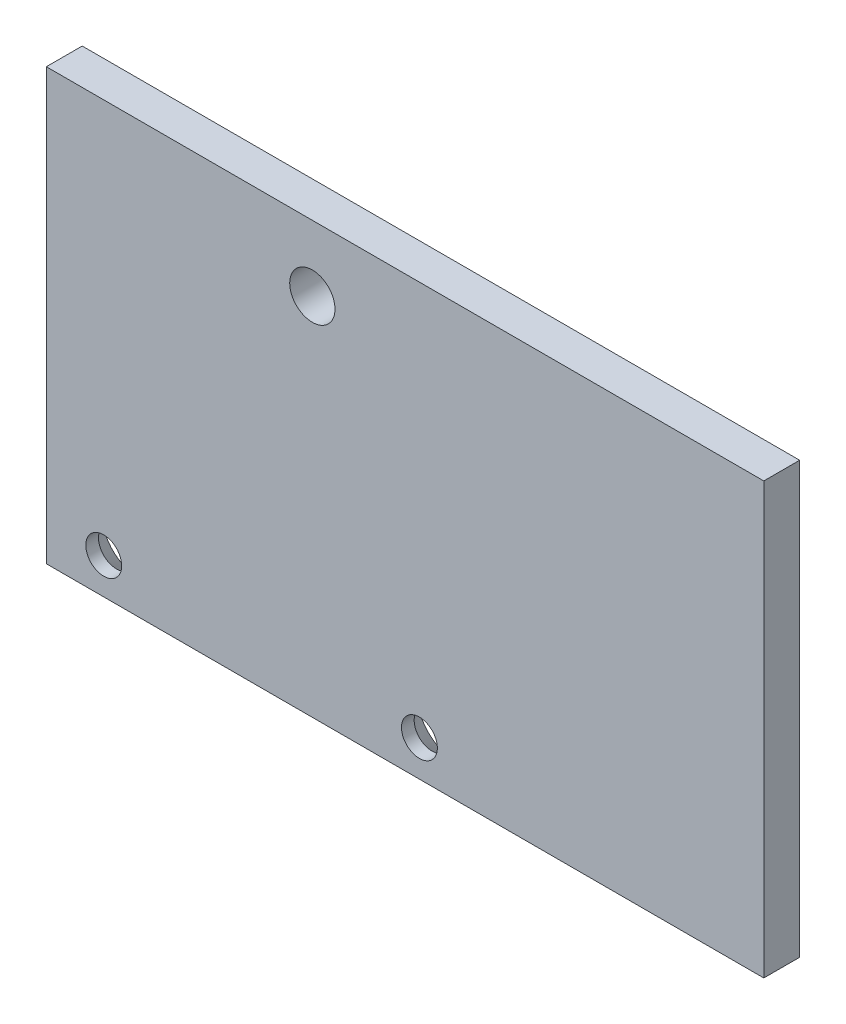
SolidWorks part; units mm, degrees
material "ABS"
ref_plane "Front Plane" through (0, 0, 0) normal (0, 0, 1) x (1, 0, 0)
ref_plane "Top Plane" through (0, 0, 0) normal (0, 1, 0) x (1, 0, 0)
ref_plane "Right Plane" through (0, 0, 0) normal (1, 0, 0) x (0, 0, -1)
sketch "Sketch1" plane through (0, 0, 0) normal (0, 0, 1) x (1, 0, 0)
  line L1 (0, 0) -> (-127, 0)
  line L2 (0, 0) -> (0, 76.2)
  line L3 (0, 76.2) -> (-127, 76.2)
  line L4 (-127, 0) -> (-127, 76.2)
  dimension "D1" = 76.2
  dimension "D2" = 127
extrude "Boss-Extrude1" add sketch "Sketch1" along normal blind 6.35
sketch "Sketch4" plane through (0, 0, 0) normal (0, 0, -1) x (-1, 0, 0)
  circle A0 centre (79.9125, 64.573) radius 4.01
  dimension "D1" = 8.02
extrude "Cut-Extrude1" cut sketch "Sketch4" against normal through all both and the other way through all
hole_wizard "1/4 (0.25) Diameter Hole1" positions "Sketch6" profile "Sketch8" hole size "1/4" standard "ANSI Inch" end condition through all
sketch "Sketch6" plane through (0, 0, 0) normal (0, 0, -1) x (-1, 0, 0)
  line L0 (127, 76.2) -> (127, 0) construction
  line L1 (127, 0) -> (0, 0) construction
  line L2 (50.8, 12.7) -> (50.8, 0) construction
  point P0 (116.84, 6.35)
  point P2 (60.96, 6.35)
  dimension "D1" = 10.16
  dimension "D2" = 6.35
  dimension "D3" = 6.35
  dimension "D4" = 10.16
sketch "Sketch8" plane through (-116.84, 6.35, 0) normal (1, 0, 0) x (0, 1, 0)
  line L0 (0, 0) -> (0, 6.35)
  line L1 (0, 6.35) -> (3.175, 6.35)
  line L2 (3.175, 6.35) -> (3.175, 4.1053)
  line L3 (3.175, 4.1053) -> (6.7437, 0)
  line L5 (6.7437, 0) -> (0, 0)
  line L6 (-3.175, 4.1053) -> (-6.7437, 0) construction
  line L11 (0, -6.35) -> (0, 107.95) construction
  dimension "Thru Hole Dia." = 6.35
  dimension "Thru Hole Depth" = 6.35
  dimension "Near C'Sink Dia." = 13.4874
  dimension "Near C'Sink Angle" = 82
